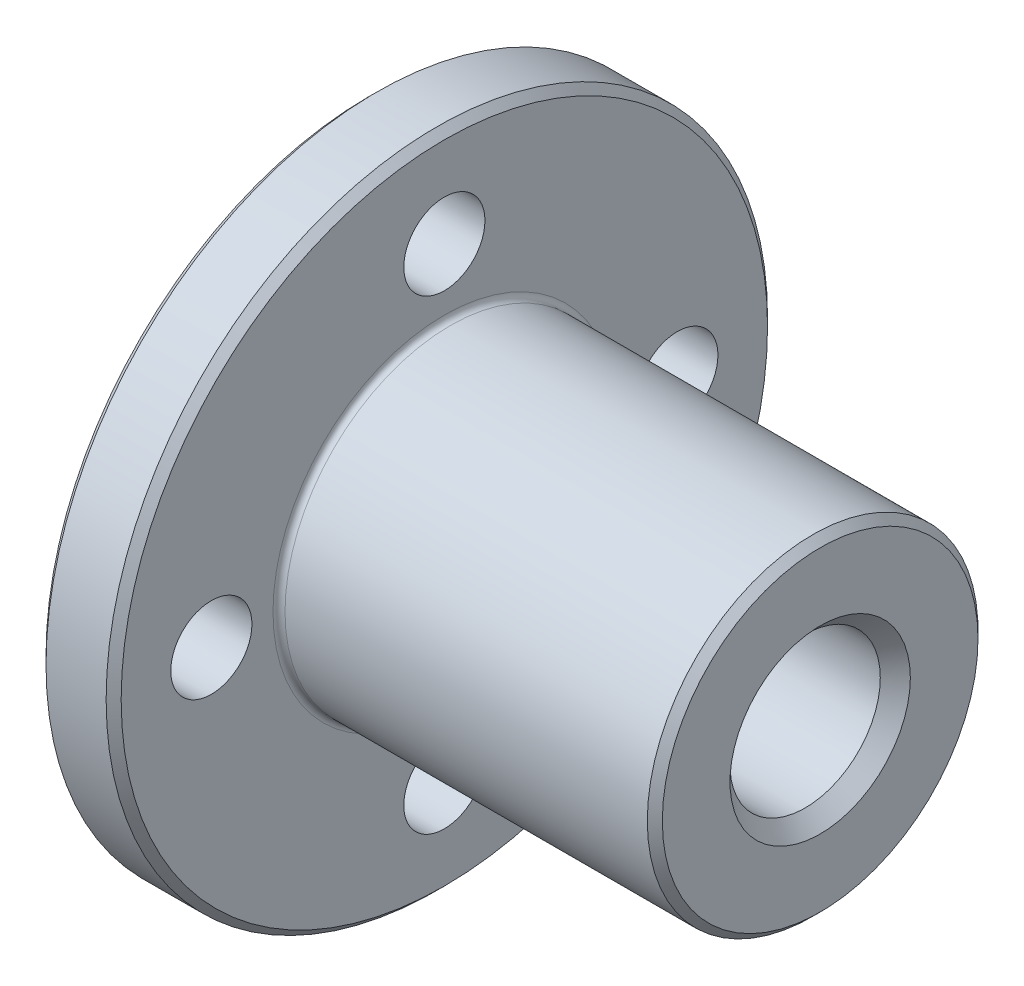
SolidWorks part; units mm, degrees
material "Ottone"
ref_plane "Piano frontale" through (0, 0, 0) normal (0, 0, 1) x (1, 0, 0)
ref_plane "Piano superiore" through (0, 0, 0) normal (0, 1, 0) x (1, 0, 0)
ref_plane "Piano destro" through (0, 0, 0) normal (1, 0, 0) x (0, 0, -1)
ref_plane "Plane1" through (0, 0, 0) normal (0, 0, -1) x (-1, 0, 0)
sketch "Sketch1" plane through (0, 0, 0) normal (0, 0, -1) x (-1, 0, 0)
  line L0 (-5, 22) -> (-5, 0)
  line L1 (-5, 0) -> (0, 0)
  line L2 (0, 0) -> (0, 22)
  line L3 (0, 22) -> (-5, 22)
  line L4 (-5, 0) -> (0, 0) construction
revolve "Revolve1" add sketch "Sketch1" angle 360 about L4 reverse direction yes
sketch "Sketch2" plane through (5, 0, 0) normal (1, 0, 0) x (0, 0, -1)
  circle A0 centre (0, 0) radius 11
extrude "Extrude1" add sketch "Sketch2" along normal blind 25
hole_wizard "HoleWzd1" positions "Sketch4" profile "Sketch3" hole size "Ø5.4" standard "Ansi Metric"
sketch "Sketch4" plane through (5, 0, 0) normal (1, 0, 0) x (0, 0, -1)
  point P0 (0, -15.5)
  point P1 (15.5, 0)
  point P2 (-15.5, 0)
  point P3 (0, 15.5)
sketch "Sketch3" plane through (5, -15.5, 0) normal (0, 1, 0) x (0, 0, -1)
  line L0 (0, 0) -> (0, 5)
  line L1 (0, 5) -> (2.7, 5)
  line L2 (2.7, 5) -> (2.7, 0)
  line L5 (2.7, 0) -> (0, 0)
  line L11 (0, -6.35) -> (0, 107.95) construction
  dimension "Thru Hole Dia." = 5.4
  dimension "Thru Hole Depth" = 5
hole_wizard "HoleWzd2" positions "Sketch6" profile "Sketch5" hole size "Ø10.0" standard "Ansi Metric"
sketch "Sketch6" plane through (30, 0, 0) normal (1, 0, 0) x (0, 0, -1)
  point P0 (0, 0)
sketch "Sketch5" plane through (30, 0, 0) normal (0, 1, 0) x (0, 0, -1)
  line L0 (0, 0) -> (0, 30)
  line L1 (0, 30) -> (5, 30)
  line L2 (5, 30) -> (5, 0)
  line L5 (5, 0) -> (0, 0)
  line L11 (0, -6.35) -> (0, 107.95) construction
  dimension "Thru Hole Dia." = 10
  dimension "Thru Hole Depth" = 30
chamfer "Chamfer1" distance 0.5 angle 45 3 edges at (0, 0, 22) (30, 0, -11) (5, 0, 22)
chamfer "Chamfer2" distance 1 angle 45 2 edges at (0, 0, -5) (30, 0, -5)
fillet "Fillet1" radius 0.4 1 edges at (5, 0, -11) tangent propagation no
